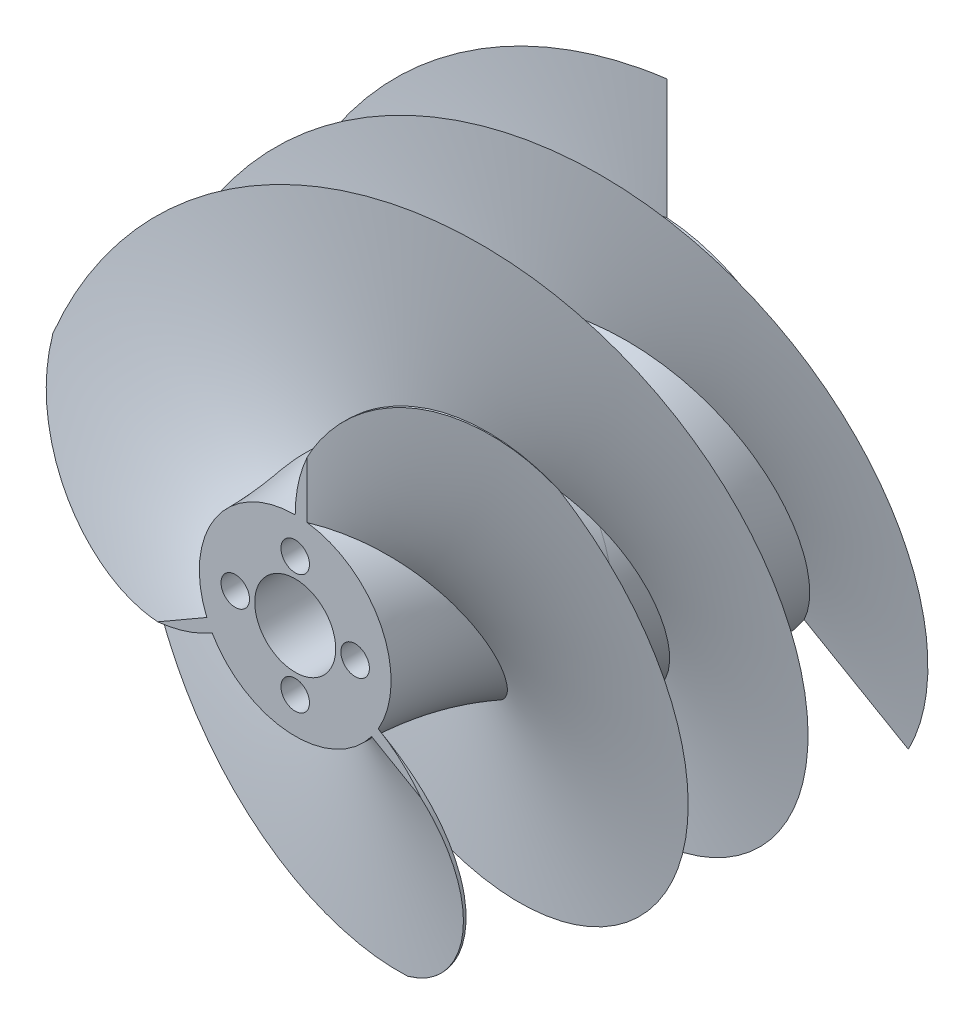
SolidWorks part; units mm, degrees
note: The reader was unsure of these and kept them because the rebuilt part matched: shared geometry of "Sketch2<3>".
material "Titanium"
ref_plane "Front Plane" through (0, 0, 0) normal (1, 0, 0) x (0, 1, 0)
ref_plane "Top Plane" through (0, 0, 0) normal (0, 0, 1) x (0, 1, 0)
ref_plane "Right Plane" through (0, 0, 0) normal (0, 1, 0) x (-1, 0, 0)
sketch "Sketch2" plane through (0, 0, 0) normal (1, 0, 0) x (0, 1, 0)
  line L0 (-3.3782, 0) -> (-3.3782, 30)
  line L1 (-3.3782, 30) -> (-8, 30)
  line L2 (-15, 0) -> (-3.3782, 0)
  line L3 (0, 0) -> (0, 30) construction
  line L4 (-25, 0) -> (-25, 30) construction
  line L5 (-15, 0) -> (-15, 30) construction
  arc A0 (-8, 30) -> (-11.5, 15) centre (-41.8929, 30) cw
  arc A1 (-11.5, 15) -> (-15, 0) centre (18.8929, 0) ccw
  dimension "D1" = 30
  dimension "D2" = 25
  dimension "D3" = 15
  dimension "D4" = 6.7564
  dimension "D5" = 8
ref_axis "Axis1" through (0, 0, 31.5) along (0, 0, -1)
revolve "Revolve1" add sketch "Sketch2" angle 360 about axis through (0, 0, 31.5) along (0, 0, -1)
sketch "Sketch3" plane through (0, 0, 30) normal (0, 0, -1) x (1, 0, 0)
  circle A0 centre (0, 0) radius 25
  dimension "D1" = 50
curve "Helix/Spiral1" pitch 30 height 30 radius 25 centre (0, 0, 30) axis (0, 0, -1) start towards (0, 1, 0)
sketch "Sketch4" plane through (0, 0, 30) normal (0, 0, 1) x (1, 0, 0)
  line L1 (18.2105, 17.1283) -> (29.5789, 8.6378) construction
  line L2 (1, 25) -> (1, 3.3782)
  line L7 (0, 0) -> (1, 0)
  line L9 (18.2105, 17.1283) -> (28.4737, 6.2166) construction
  line L10 (0, 0) -> (18.2105, 17.1283) construction
  line L11 (0, 18.755) -> (0, 3.3782)
  line L12 (0, 3.3782) -> (1, 3.3782)
  arc A0 (1, 25) -> (0, 18.755) centre (20, 18.755) ccw
  arc A1 (0, 8) -> (18.2105, 17.1283) centre (11.3931, 8) cw construction
  circle A2 centre (0, 0) radius 8 construction
  circle A5 centre (0, 0) radius 3.3782 construction
  dimension "D3" = 1
  dimension "D4" = 20
  dimension "D5" = 10
  dimension "D1" = 25
  dimension "D2" = 25
sweep "Sweep2" add profiles "Sketch4" path "Helix/Spiral1"
sketch "Sketch6" plane through (0, 0, 30) normal (0, 0, 1) x (1, 0, 0)
  line L0 (0, 0) -> (18.2105, 17.1283) construction
  line L1 (0, 8) -> (-28.9137, 8)
  line L2 (0, 18.755) -> (0, 8) construction
  line L3 (18.2105, 17.1283) -> (27.6007, 10.1152) construction
  line L4 (18.2105, 17.1283) -> (26.8533, 7.9394) construction
  line L5 (18.2105, 17.1283) -> (21.8526, 20.5539)
  arc A0 (0, 8) -> (18.2105, 17.1283) centre (11.3931, 8) cw
  arc A2 (21.8526, 20.5539) -> (-28.9137, 8) centre (0, 0) ccw
  dimension "D1" = 25
  dimension "D2" = 10
  dimension "D3" = 5
extrude "Cut-Extrude1" cut sketch "Sketch6" against normal blind 10 contours L1 A2 L5 A0
pattern_circular "CirPattern4" count 3 over 360 about axis through (0, 0, 31.5) along (0, 0, -1)
revolve "Revolve3" add sketch "Sketch2<3>" angle 360 about axis through (0, 0, 31.5) along (0, 0, -1)
sketch "Sketch2<3>" plane through (0, 0, 0) normal (1, 0, 0) x (0, 1, 0) same geometry as "Sketch2"
sketch "Sketch7" plane through (0, 0, 0) normal (0, 0, -1) x (1, 0, 0)
  line L0 (-5, 0) -> (5, 0) construction
  line L1 (0, -5) -> (0, 5) construction
  circle A0 centre (0, 5) radius 1.1906
  circle A1 centre (5, 0) radius 1.1906
  circle A2 centre (0, -5) radius 1.1906
  circle A3 centre (-5, 0) radius 1.1906
  dimension "D1" = 2.3812
  dimension "D2" = 10
extrude "Cut-Extrude2" cut sketch "Sketch7" against normal through all
